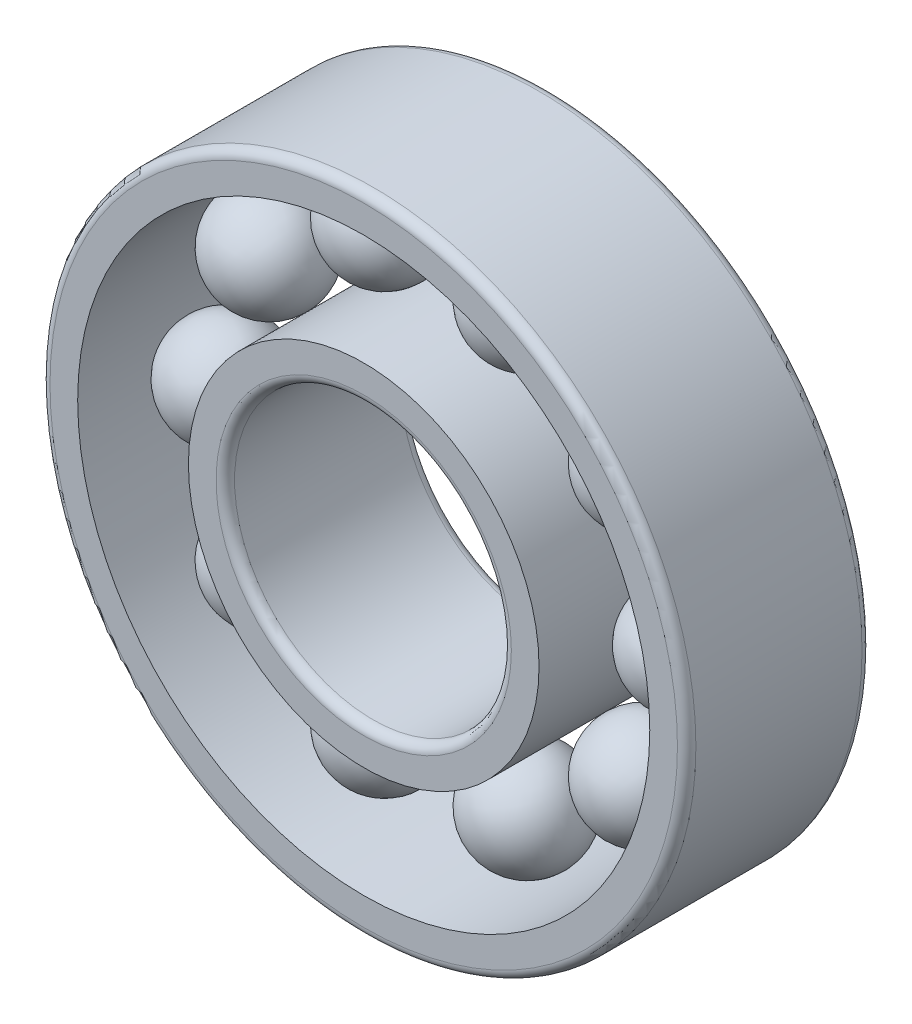
SolidWorks part; units mm, degrees
ref_plane "Front Plane" through (0, 0, 0) normal (0, 0, 1) x (1, 0, 0)
ref_plane "Top Plane" through (0, 0, 0) normal (0, 1, 0) x (1, 0, 0)
ref_plane "Right Plane" through (0, 0, 0) normal (1, 0, 0) x (0, 0, -1)
sketch "S" plane through (0, 0, 0) normal (0, 0, 1) x (1, 0, 0)
  line L0 (-1, 0) -> (1, 0) construction
  circle A0 centre (0, 0) radius 1.5 construction
  circle A1 centre (0, 0) radius 3.5 construction
  circle A2 centre (0, 0) radius 1.9 construction
  circle A3 centre (0, 0) radius 3.1 construction
  dimension "ID" = 3
  dimension "OD" = 7
  dimension "IDa" = 3.8
  dimension "ODa" = 6.2
  dimension "B" = 2
ref_axis "Z" through (0, 0, -1.1) along (0, 0, 1)
sketch "InnerS" plane through (0, 0, 0) normal (0, 1, 0) x (1, 0, 0)
  line L0 (1.5, -1) -> (1.9, -1)
  line L1 (1.9, -1) -> (1.9, 1)
  line L2 (1.9, 1) -> (1.5, 1)
  line L3 (1.5, 1) -> (1.5, -1)
  line L4 (0, -2.5) -> (0, 2.5) construction
  dimension "r1" = 1.5
  dimension "r2" = 1.9
  dimension "z1" = 1
  dimension "z2" = 1
revolve "InnerRing" add sketch "InnerS" angle 360 about L4
sketch "OuterS" plane through (0, 0, 0) normal (0, 1, 0) x (1, 0, 0)
  line L0 (3.1, -1) -> (3.5, -1)
  line L1 (3.5, -1) -> (3.5, 1)
  line L2 (3.5, 1) -> (3.1, 1)
  line L3 (3.1, 1) -> (3.1, -1)
  line L4 (0, -2.5) -> (0, 2.5) construction
  dimension "r1" = 3.1
  dimension "r2" = 3.5
  dimension "z1" = 1
  dimension "z2" = 1
revolve "OuterRing" add sketch "OuterS" angle 360 about L4
sketch "BallS" plane through (0, 0, 0) normal (0, 1, 0) x (1, 0, 0)
  line L0 (1.93, 0) -> (3.07, 0)
  arc A0 (1.93, 0) -> (3.07, 0) centre (2.5, 0) ccw
  dimension "r" = 0.57
  dimension "p" = 2.5
revolve "Ball" add sketch "BallS" angle 360 about L0
pattern_circular "BallsPattern" count 10 over 360 about axis through (0, 0, -1.1) along (0, 0, 1) of bodies 103
fillet "F1" radius 0.1 2 edges at (1.5, 0, -1) (1.5, 0, 1)
fillet "F2" radius 0.1 2 edges at (3.5, 0, -1) (3.5, 0, 1)
equation "\"r1@InnerS\" = abs(0.5*\"ID@S\")"
equation "\"r2@InnerS\" = abs(0.5*\"IDa@S\")"
equation "\"z1@InnerS\" = abs(-0.5*\"B@S\")"
equation "\"z2@InnerS\" = abs(0.5*\"B@S\")"
equation "\"r1@OuterS\" = abs(0.5*\"ODa@S\")"
equation "\"r2@OuterS\" = abs(0.5*\"OD@S\")"
equation "\"z1@OuterS\" = abs(-0.5*\"B@S\")"
equation "\"z2@OuterS\" = abs(0.5*\"B@S\")"
equation "\"r@BallS\" = abs(0.2375*\"ODa@S\"-0.2375*\"IDa@S\")"
equation "\"p@BallS\" = abs(0.25*\"IDa@S\"+0.25*\"ODa@S\")"
equation "\"N@BallsPattern\" = int(2.417*(0.25*\"IDa@S\"+0.25*\"ODa@S\")/(0.2375*\"ODa@S\"-0.2375*\"IDa@S\"))"
equation "\"r_min@F2\" = \"r_min@F1\""
